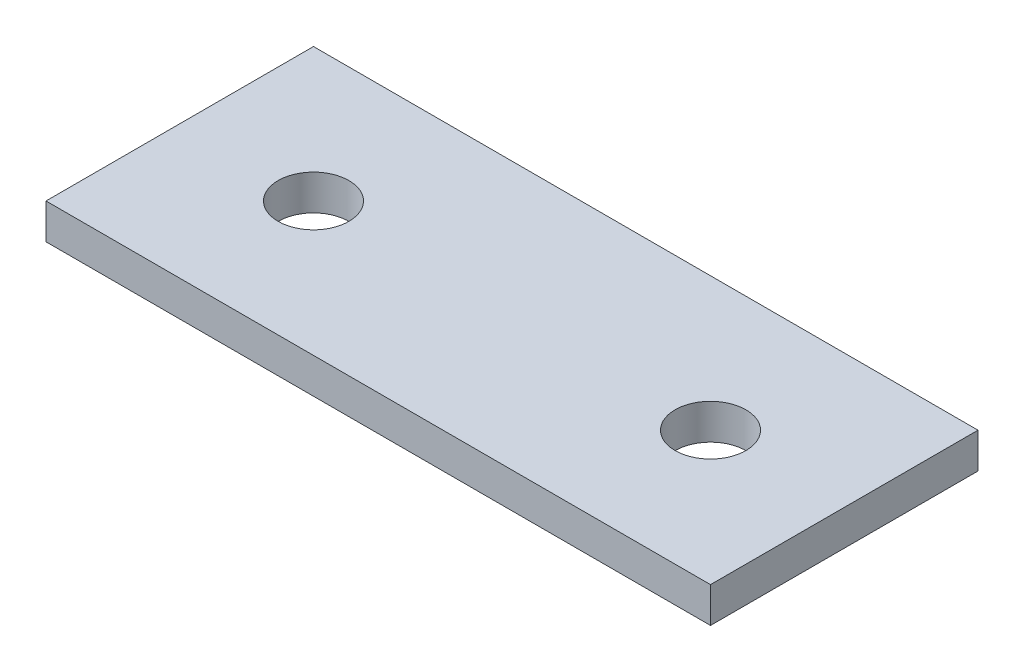
SolidWorks part; units mm, degrees
ref_plane "Front Plane" through (0, 0, 0) normal (0, 0, 1) x (1, 0, 0)
ref_plane "Top Plane" through (0, 0, 0) normal (0, 1, 0) x (1, 0, 0)
ref_plane "Right Plane" through (0, 0, 0) normal (1, 0, 0) x (0, 0, -1)
sketch "Sketch1" plane through (0, 0, 0) normal (0, 1, 0) x (1, 0, 0)
  line L0 (-8.905, 0) -> (8.905, 0) construction
  line L1 (14.905, -6) -> (-14.905, -6)
  line L2 (14.905, -6) -> (14.905, 6)
  line L3 (14.905, 6) -> (-14.905, 6)
  line L4 (-14.905, -6) -> (-14.905, 6)
  line L5 (14.905, -6) -> (-14.905, 6) construction
  line L6 (14.905, 6) -> (-14.905, -6) construction
  circle A0 centre (-8.905, 0) radius 1.5875
  circle A1 centre (8.905, 0) radius 1.5875
  circle A2 centre (-8.905, 0) radius 5 construction
  point P0 (0, 0)
  point P8 (0, 0)
  dimension "D1" = 3.175
  dimension "D4" = 10
  dimension "D2" = 17.81
  dimension "D3" = 12
  dimension "D5" = 6
extrude "Boss-Extrude1" add sketch "Sketch1" along normal mid plane 1.5875
